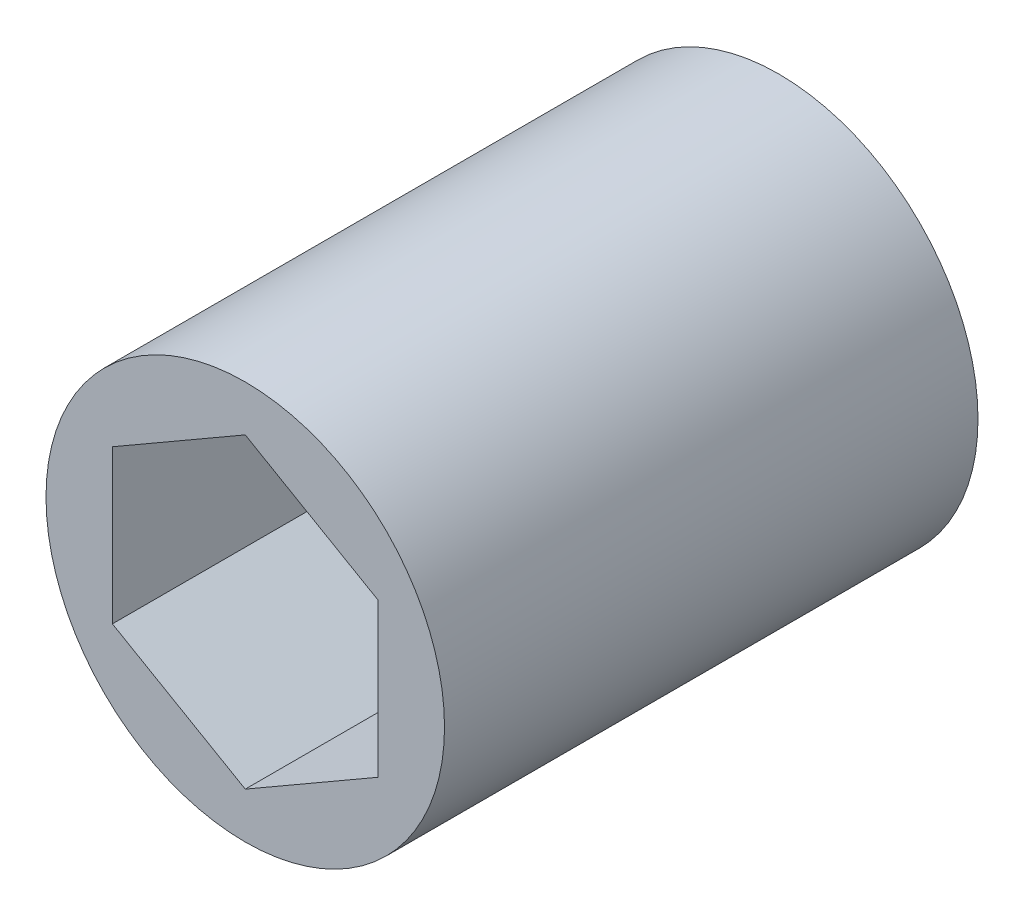
SolidWorks part; units mm, degrees
material "Nylon 101"
ref_plane "Front Plane" through (0, 0, 0) normal (0, 0, 1) x (1, 0, 0)
ref_plane "Top Plane" through (0, 0, 0) normal (0, 1, 0) x (1, 0, 0)
ref_plane "Right Plane" through (0, 0, 0) normal (1, 0, 0) x (0, 0, -1)
sketch "Sketch1" plane through (0, 0, 0) normal (0, 0, 1) x (1, 0, 0)
  line L1 (0, 7.3323) -> (-6.35, 3.6662)
  line L2 (-6.35, 3.6662) -> (-6.35, -3.6662)
  line L3 (-6.35, -3.6662) -> (0, -7.3323)
  line L4 (0, -7.3323) -> (6.35, -3.6662)
  line L5 (6.35, -3.6662) -> (6.35, 3.6662)
  line L6 (6.35, 3.6662) -> (0, 7.3323)
  circle A0 centre (0, 0) radius 9.525
  circle A1 centre (0, 0) radius 6.35 construction
  dimension "D1" = 19.05
  dimension "D2" = 12.7
extrude "Boss-Extrude1" add sketch "Sketch1" along normal blind 25.5016
